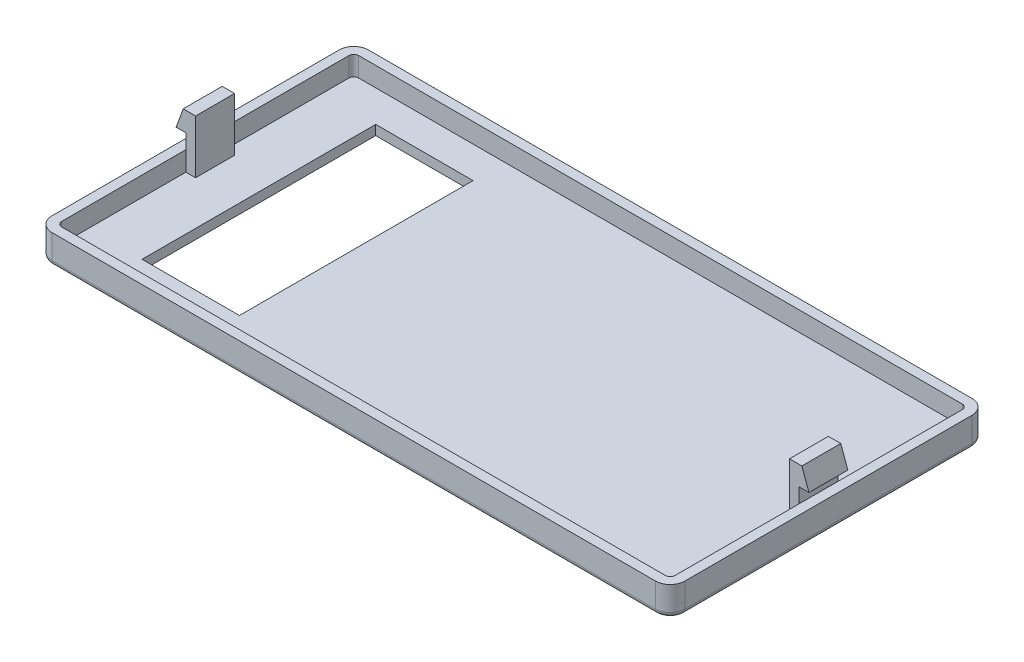
SolidWorks part; units mm, degrees
material "ABS"
ref_plane "Front Plane" through (0, 0, 0) normal (0, 0, 1) x (1, 0, 0)
ref_plane "Top Plane" through (0, 0, 0) normal (0, 1, 0) x (1, 0, 0)
ref_plane "Right Plane" through (0, 0, 0) normal (1, 0, 0) x (0, 0, -1)
sketch "Эскиз1" plane through (0, 0, 0) normal (0, 1, 0) x (1, 0, 0)
  line L1 (-65, -32.5) -> (65, -32.5)
  line L2 (-65, -32.5) -> (-65, 32.5)
  line L3 (-65, 32.5) -> (65, 32.5)
  line L4 (65, -32.5) -> (65, 32.5)
  line L5 (-65, -32.5) -> (65, 32.5) construction
  line L6 (-65, 32.5) -> (65, -32.5) construction
  point P0 (0, 0)
extrude "Бобышка-Вытянуть1" add sketch "Эскиз1" along normal blind 6
sketch "Эскиз2" plane through (0, 6, 0) normal (0, 1, 0) x (1, 0, 0)
  line L1 (-63, -30.5) -> (63, -30.5)
  line L2 (-63, -30.5) -> (-63, 30.5)
  line L3 (-63, 30.5) -> (63, 30.5)
  line L4 (63, -30.5) -> (63, 30.5)
  line L5 (-63, -30.5) -> (63, 30.5) construction
  line L6 (-63, 30.5) -> (63, -30.5) construction
  point P0 (0, 0)
extrude "Вырез-Вытянуть1" cut sketch "Эскиз2" against normal blind 4
sketch "Эскиз6" plane through (0, 2, 0) normal (0, 1, 0) x (1, 0, 0)
  line L1 (63, 0) -> (62, 0)
  line L2 (63, -30.5) -> (63, 30.5) construction
  line L4 (63, -4) -> (61, -4)
  line L5 (63, -4) -> (63, 4)
  line L6 (63, 4) -> (61, 4)
  line L7 (61, -4) -> (61, 4)
  line L8 (63, -4) -> (61, 4) construction
  line L9 (63, 4) -> (61, -4) construction
fillet "Скругление1" radius 1 4 edges at (65, 0, 0) (0, 0, 32.5) (0, 0, -32.5) (-65, 0, 0)
sketch "Эскиз9" plane through (0, 0, 0) normal (0, -1, 0) x (1, 0, 0)
  line L0 (0, 0) -> (-42, 0)
  line L2 (-32, -24) -> (-52, -24)
  line L3 (-32, -24) -> (-32, 24)
  line L4 (-32, 24) -> (-52, 24)
  line L5 (-52, -24) -> (-52, 24)
  line L6 (-32, -24) -> (-52, 24) construction
  line L7 (-32, 24) -> (-52, -24) construction
extrude "Вырез-Вытянуть3" cut sketch "Эскиз9" against normal blind 2 contours L5 L4 L3 L2
extrude "Бобышка-Вытянуть2" add sketch "Эскиз6" along normal blind 11
sketch "Эскиз12" plane through (63, 0, 0) normal (1, 0, 0) x (0, 0, -1)
  line L0 (-4, 13) -> (-4, 6) construction
  line L1 (4, 13) -> (-4, 13)
  line L2 (4, 13) -> (4, 9)
  line L3 (4, 9) -> (-4, 9)
  line L4 (-4, 13) -> (-4, 9)
extrude "Бобышка-Вытянуть4" add sketch "Эскиз12" along normal blind 2
chamfer "Фаска2" distance 4 angle 20 1 edges at (65, 13, 0)
mirror "Зеркальное отражение2" about plane through (0, 0, 0) normal (1, 0, 0) of "Фаска2", "Бобышка-Вытянуть4", "Бобышка-Вытянуть2"
fillet "Скругление2" radius 1 4 edges at (-63, 4, -30.5) (-63, 4, 30.5) (63, 4, 30.5) (63, 4, -30.5)
fillet "Скругление3" radius 3 8 edges at (-64.7071, 0.2929, 32.2071) (-64.7071, 0.2929, -32.2071) (64.7071, 0.2929, -32.2071) (64.7071, 0.2929, 32.2071) (65, 3.5, 32.5) (65, 3.5, -32.5) (-65, 3.5, -32.5) (-65, 3.5, 32.5)
